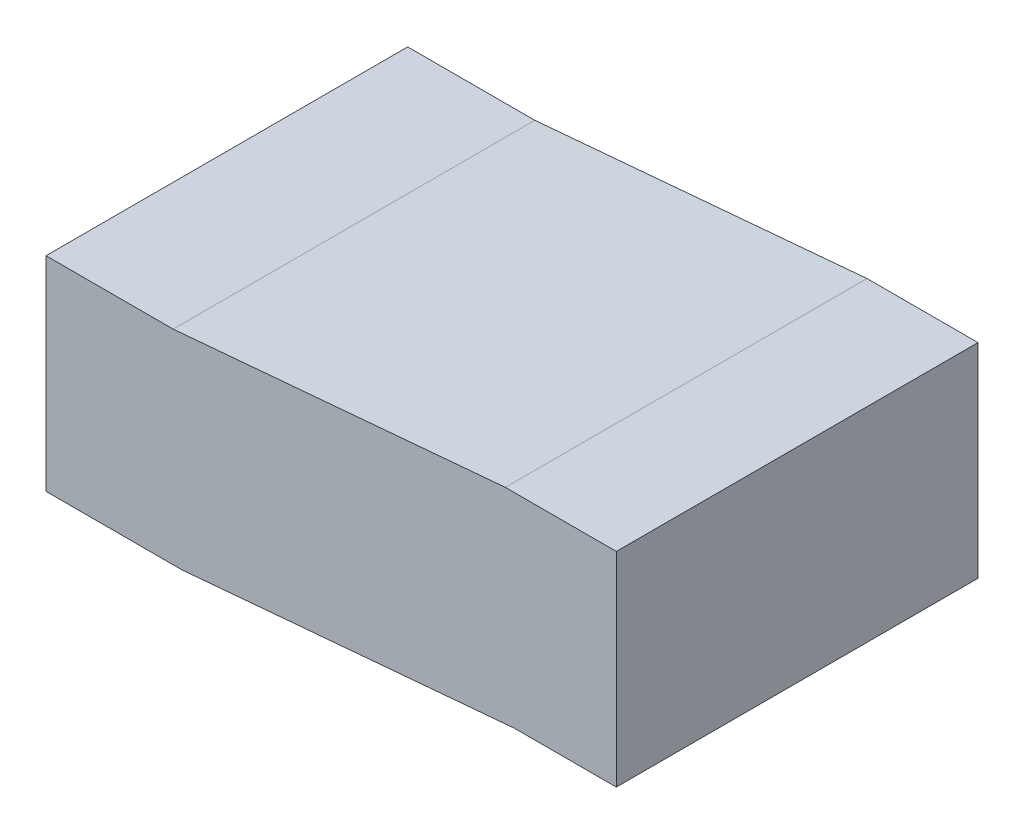
SolidWorks part; units mm, degrees
ref_plane "Front" through (0, 0, 0) normal (0, 0, 1) x (1, 0, 0)
ref_plane "Top" through (0, 0, 0) normal (0, 1, 0) x (1, 0, 0)
ref_plane "Right" through (0, 0, 0) normal (1, 0, 0) x (0, 0, -1)
sketch "Sketch2" plane through (0, 0, 0) normal (0, 0, 1) x (1, 0, 0)
  line L0 (0, 0) -> (2000, 0)
  line L1 (2000, 0) -> (6882.5, 427.1634)
  line L2 (6882.5, 427.1634) -> (8382.5, 427.1634)
  line L3 (2000, 0) -> (100.203, 0) construction
  line L4 (0, 3000) -> (1869.0172, 3000)
  line L5 (1869.0172, 3000) -> (6751.5172, 3427.1634)
  line L6 (6751.5172, 3427.1634) -> (8382.5, 3427.1634)
  line L7 (0, 3000) -> (0, 0)
  line L8 (8382.5, 3427.1634) -> (8382.5, 427.1634)
  dimension "D1" = 5
  dimension "D2" = 8382.5
  dimension "D3" = 2000
  dimension "D4" = 1500
  dimension "D5" = 3000
extrude "Boss-Extrude1" add sketch "Sketch2" along normal blind 5316
